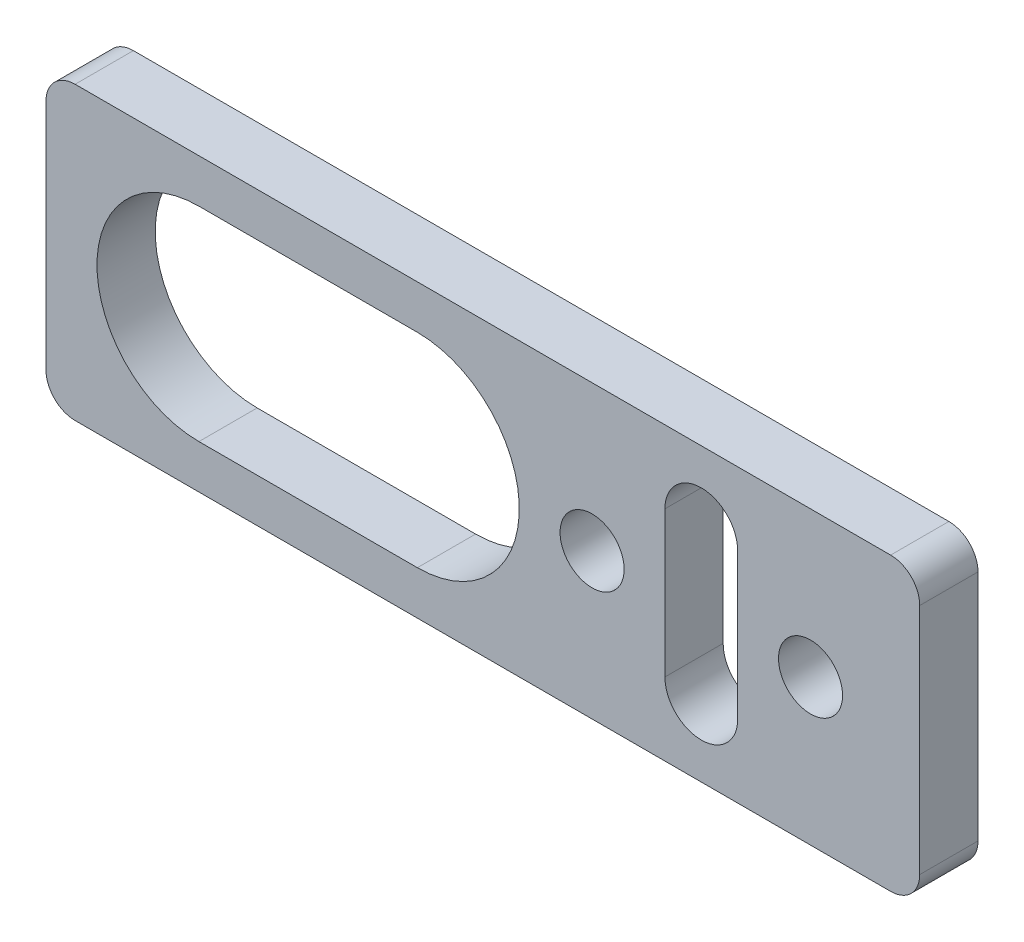
SolidWorks part; units mm, degrees
ref_plane "前视基准面" through (0, 0, 0) normal (0, 0, 1) x (1, 0, 0)
ref_plane "上视基准面" through (0, 0, 0) normal (0, 1, 0) x (1, 0, 0)
ref_plane "右视基准面" through (0, 0, 0) normal (1, 0, 0) x (0, 0, -1)
sketch "草图1" plane through (0, 0, 0) normal (0, 0, 1) x (1, 0, 0)
  line L1 (-30, -10) -> (30, -10)
  line L2 (-30, -10) -> (-30, 10)
  line L3 (-30, 10) -> (30, 10)
  line L4 (30, -10) -> (30, 10)
  line L5 (-30, -10) -> (30, 10) construction
  line L6 (-30, 10) -> (30, -10) construction
  point P0 (0, 0)
  dimension "D1" = 20
  dimension "D2" = 60
extrude "凸台-拉伸1" add sketch "草图1" along normal blind 4
fillet "圆角1" radius 2 4 edges at (30, 10, 2) (30, -10, 2) (-30, -10, 2) (-30, 10, 2)
sketch "草图2" plane through (0, 0, 4) normal (0, 0, 1) x (1, 0, 0)
  line L0 (0, 0) -> (50000, 0) construction
  line L1 (30, -8) -> (30, 8) construction
  circle A0 centre (22.5, 0) radius 2.2
  circle A1 centre (7.5, 0) radius 2.2
  dimension "D1" = 4.4
  dimension "D2" = 4.4
  dimension "D3" = 7.5
  dimension "D4" = 15
extrude "切除-拉伸1" cut sketch "草图2" against normal through all
sketch "草图3" plane through (0, 0, 4) normal (0, 0, 1) x (1, 0, 0)
  line L0 (-19.5, 0) -> (-4.5, 0) construction
  line L1 (-19.5, 7) -> (-4.5, 7)
  line L2 (-19.5, -7) -> (-4.5, -7)
  line L3 (15, -5) -> (15, 5) construction
  line L6 (12.5, -5) -> (12.5, 5)
  line L7 (17.5, -5) -> (17.5, 5)
  line L8 (7.5, 0) -> (22.5, 0) construction
  arc A0 (-19.5, 7) -> (-19.5, -7) centre (-19.5, 0) ccw
  arc A1 (-4.5, -7) -> (-4.5, 7) centre (-4.5, 0) ccw
  arc A4 (12.5, -5) -> (17.5, -5) centre (15, -5) ccw
  arc A5 (17.5, 5) -> (12.5, 5) centre (15, 5) ccw
  point P3 (-12, 0)
  point P10 (15, 0)
  dimension "D1" = 7
  dimension "D5" = 2.5
  dimension "D2" = 15
  dimension "D3" = 12
  dimension "D4" = 10
extrude "切除-拉伸2" cut sketch "草图3" against normal through all
